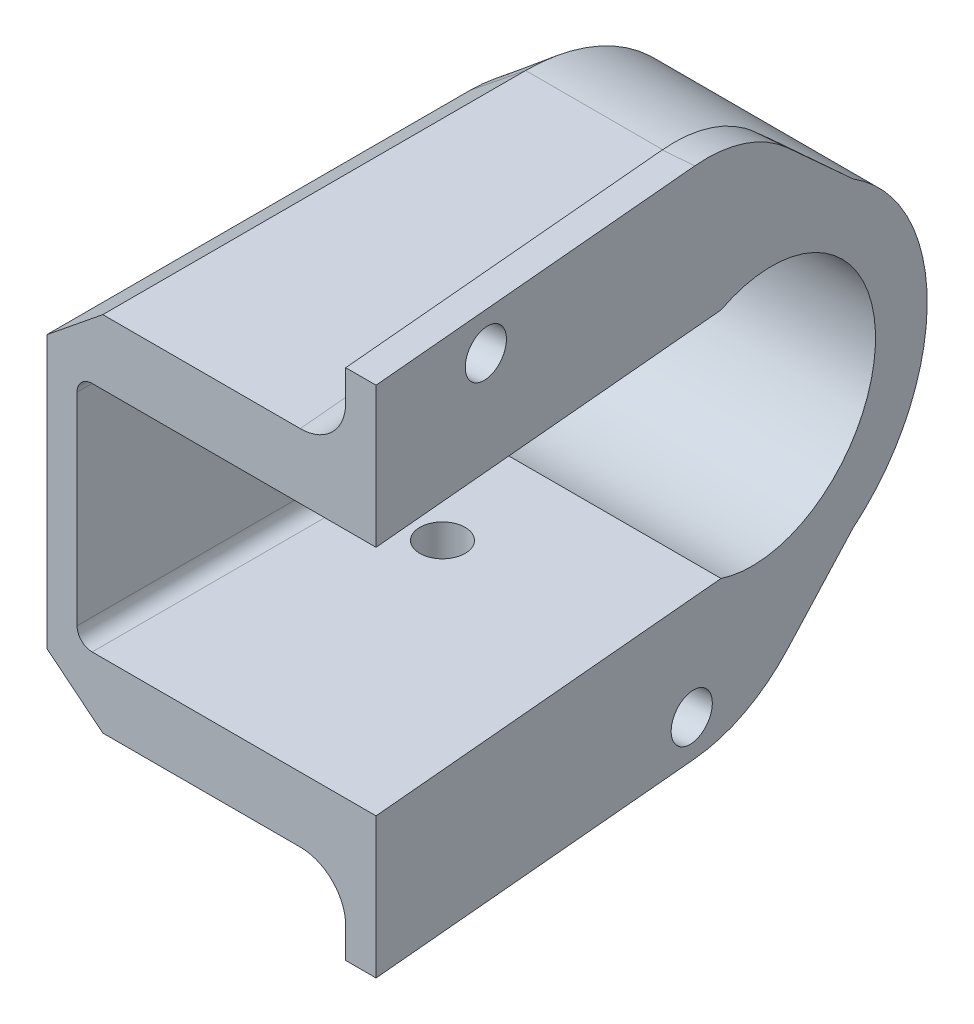
SolidWorks part; units mm, degrees
ref_plane "Front Plane" through (0, 0, 0) normal (0, 0, 1) x (1, 0, 0)
ref_plane "Top Plane" through (0, 0, 0) normal (0, 1, 0) x (1, 0, 0)
ref_plane "Right Plane" through (0, 0, 0) normal (1, 0, 0) x (0, 0, -1)
sketch "Sketch1" plane through (0, 0, 0) normal (1, 0, 0) x (0, 0, -1)
  line L0 (40, 12) -> (0, 12) construction
  line L1 (0, 0) -> (28, 0)
  line L2 (0, 0) -> (0, 24)
  line L3 (0, 24) -> (28, 24)
  arc A0 (28, 0) -> (28, 24) centre (28, 12) ccw
  dimension "D2" = 12
  dimension "D1" = 28
extrude "Boss-Extrude1" add sketch "Sketch1" along normal blind 2
sketch "Sketch2" plane through (2, 0, 0) normal (1, 0, 0) x (0, 0, -1)
  line L0 (0, 24) -> (0, 19.7)
  line L1 (0, 24) -> (0, 0) construction
  line L5 (40, 12) -> (0, 12) construction
  line L9 (0, 19.7) -> (25.0382, 19.7)
  line L10 (0, 24) -> (28, 24)
  line L11 (0, 0) -> (28, 0)
  line L12 (0, 4.3) -> (25.0382, 4.3)
  line L13 (0, 0) -> (0, 4.3)
  arc A3 (28, 24) -> (28, 0) centre (28, 12) cw
  arc A5 (25.0382, 4.3) -> (25.0382, 19.7) centre (28, 12) ccw
  dimension "D1" = 16.5
  dimension "D2" = 40
  dimension "D4" = 7.7
extrude "Boss-Extrude3" add sketch "Sketch2" along normal blind 20
sketch "Sketch3" plane through (0, 24, 0) normal (0, 1, 0) x (1, 0, 0)
  line L0 (21.8, 0) -> (18.3005, 40)
  line L1 (22, 0) -> (0, 0) construction
  line L2 (22, 40) -> (0, 40) construction
  line L3 (18.3005, 40) -> (22, 40)
  line L4 (22, 40) -> (22, 0)
  line L5 (22, 0) -> (21.8, 0)
  dimension "D1" = 0.2
  dimension "D2" = 5
extrude "Cut-Extrude1" cut sketch "Sketch3" against normal through all
sketch "Sketch8" plane through (21.6344, 0, -1.8928) normal (0.9962, 0, -0.0872) x (-0.0872, 0, -0.9962)
  line L0 (-1.9, 24) -> (26.207, 24)
  line L1 (32.8529, 22.0084) -> (28.0775, 26.3777)
  line L2 (21.327, 29) -> (-1.9, 29)
  line L3 (-1.9, 29) -> (-1.9, 24)
  line L4 (-0.1743, 12) -> (39.8478, 12) construction
  line L5 (-0.1743, 19.7) -> (-0.1743, 4.3) construction
  line L6 (-1.9, -5) -> (-1.9, 0)
  line L7 (21.327, -5) -> (-1.9, -5)
  line L8 (32.8529, 1.9916) -> (28.0775, -2.3777)
  line L9 (-1.9, 0) -> (26.207, 0)
  arc A0 (26.207, 24) -> (32.8529, 22.0084) centre (26.207, 11.9158) cw
  arc A1 (28.0775, 26.3777) -> (21.327, 29) centre (21.327, 19) ccw
  arc A2 (28.0775, -2.3777) -> (21.327, -5) centre (21.327, 5) cw
  arc A3 (26.207, 0) -> (32.8529, 1.9916) centre (26.207, 12.0842) ccw
  ellipse E0 centre (26.207, 12) end of major axis (38.2528, 12) minor radius 12 (26.207, 0) -> (26.207, 24) ccw construction
  ellipse E1 centre (27.8935, 12) end of major axis (27.8935, 24) minor radius 11.9543 (27.8935, 0) -> (27.8935, 24) ccw construction
  dimension "D2" = 10
  dimension "D1" = 5
extrude "Boss-Extrude6" add sketch "Sketch8" against normal blind 2
fillet "Fillet2" radius 3 4 edges at (18.5675, 0, -14) (17.0672, 0.4205, -31.149) (18.5675, 24, -14) (17.0672, 23.5795, -31.149)
sketch "Sketch9" plane through (0, 0, 0) normal (0, 0, 1) x (1, 0, 0)
  line L1 (-2.5102, 30.3092) -> (26.5678, 30.3092)
  line L2 (-2.5102, 30.3092) -> (-2.5102, -6.3092)
  line L3 (-2.5102, -6.3092) -> (26.5678, -6.3092)
  line L4 (26.5678, 30.3092) -> (26.5678, -6.3092)
extrude "Cut-Extrude3" cut sketch "Sketch9" along normal through all
ref_plane "Plane2" through (21.8336, 0, -1.9102) normal (0.9962, 0, -0.0872) x (-0.0872, 0, -0.9962)
sketch "Sketch10" plane through (21.8336, 0, -1.9102) normal (0.9962, 0, -0.0872) x (-0.0872, 0, -0.9962)
  line L1 (21.327, 29) -> (-1.725, 29) construction
  line L2 (-1.725, -5) -> (21.327, -5) construction
  line L3 (-1.9, 19.7) -> (-1.9, 29) construction
  circle A1 centre (21.1, -2.5) radius 1.5
  circle A2 centre (6.1, 26.5) radius 1.5
  dimension "D1" = 3
  dimension "D2" = 2.5
  dimension "D3" = 2.5
  dimension "D4" = 15
  dimension "D5" = 8
extrude "Cut-Extrude4" cut sketch "Sketch10" against normal up to next
chamfer "Chamfer1" distance 3 angle 51 3 edges at (0, 24, -14) (0, 12, -40) (0, 0, -14) first distance on face at (0, 12, -17)
fillet "Fillet3" radius 1 3 edges at (2, 19.7, -12.5191) (2, 4.3, -12.5191) (2, 12, -36.25)
sketch "Sketch13" plane through (0, 0, 0) normal (0, -1, 0) x (1, 0, 0)
  line L0 (0, -28) -> (0, 0) construction
  line L1 (3.7047, -40) -> (18.3005, -40) construction
  circle A0 centre (8.2, -18) radius 1.5
  dimension "D3" = 3
  dimension "D1" = 8.2
  dimension "D2" = 22
extrude "Cut-Extrude5" cut sketch "Sketch13" against normal up to next
